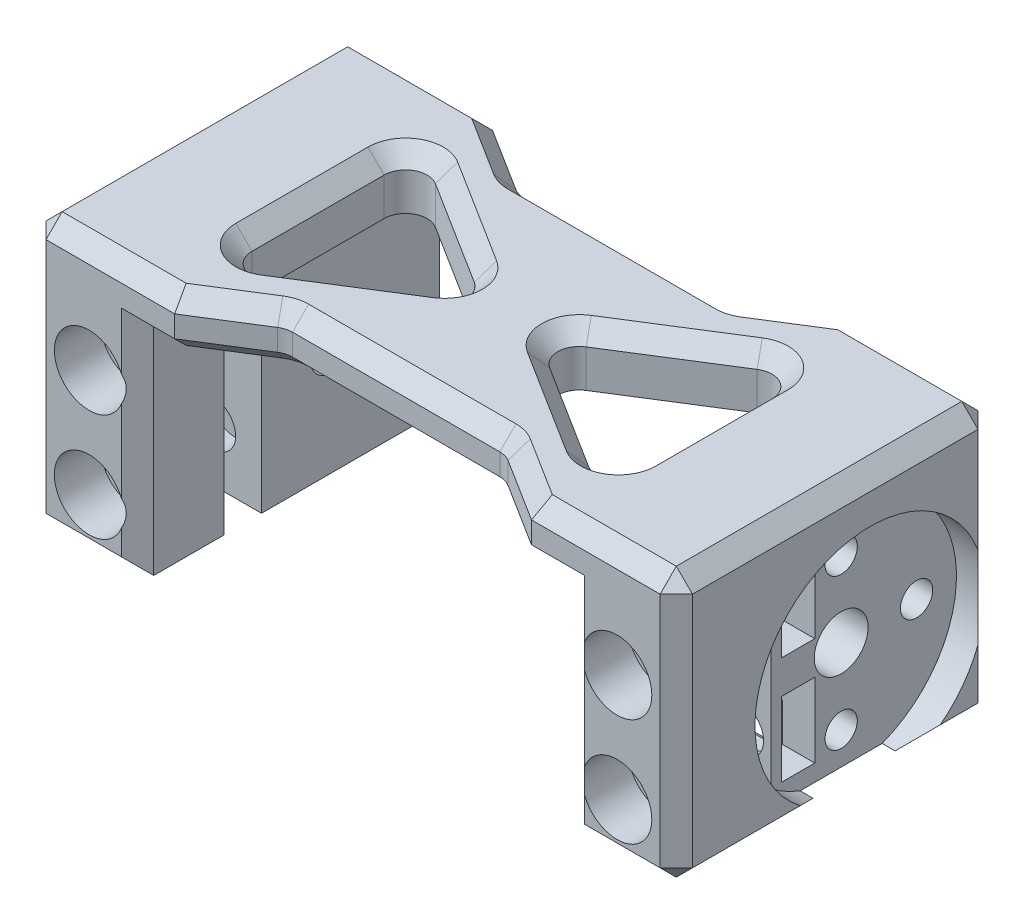
SolidWorks part; units mm, degrees
ref_plane "Ebene vorne" through (0, 0, 0) normal (0, 0, 1) x (1, 0, 0)
ref_plane "Ebene oben" through (0, 0, 0) normal (0, 1, 0) x (1, 0, 0)
ref_plane "Ebene rechts" through (0, 0, 0) normal (1, 0, 0) x (0, 0, -1)
sketch "Sketch1" plane through (0, 0, 0) normal (0, 0, 1) x (1, 0, 0)
  line L0 (-24.5, 10) -> (-24.5, -10) construction
  line L5 (30, -10) -> (20, -10)
  line L6 (30, -10) -> (30, 10)
  line L11 (30, 10) -> (-30, 10)
  line L12 (-30, -10) -> (-30, 10)
  line L21 (30, -10) -> (-30, 10) construction
  line L23 (30, 10) -> (-30, -10) construction
  line L29 (24.5, 10) -> (24.5, -10) construction
  line L30 (-20, -10) -> (-30, -10)
  line L32 (20, -10) -> (20, 10)
  line L33 (20, 10) -> (-20, 10)
  line L35 (-20, -10) -> (-20, 10)
  line L36 (20, -10) -> (-20, 10) construction
  line L37 (20, 10) -> (-20, -10) construction
  line L39 (-30, 10) -> (30, 10)
  line L40 (-30, 10) -> (-30, 15)
  line L41 (-30, 15) -> (30, 15)
  line L42 (30, 10) -> (30, 15)
  circle A4 centre (-24.5, 5) radius 2.1
  circle A5 centre (-24.5, -5) radius 2.1
  circle A6 centre (24.5, 5) radius 2.1
  circle A7 centre (24.5, -5) radius 2.1
  point P0 (0, 0)
  point P10 (-24.5, 0)
  point P12 (0, 0)
  dimension "D7" = 5
  dimension "D11" = 4.2
  dimension "D1" = 60
  dimension "D2" = 20
  dimension "D3" = 24.5
  dimension "D4" = 24.5
  dimension "D5" = 40
  dimension "D6" = 5
  dimension "D8" = 5
  dimension "D9" = 10
  dimension "D10" = 10
extrude "Boss-Extrude1" add sketch "Sketch1" against normal blind 8
sketch "Sketch5" plane through (0, 0, -8) normal (0, 0, -1) x (-1, 0, 0)
  line L0 (30, -10) -> (30, 15) construction
  line L2 (27.75, -10) -> (27.75, 10)
  line L3 (27.75, 10) -> (-27.75, 10)
  line L4 (-27.75, -10) -> (-27.75, 10)
  line L5 (27.75, -10) -> (-27.75, 10) construction
  line L6 (27.75, 10) -> (-27.75, -10) construction
  line L7 (-30, -10) -> (-30, 15) construction
  line L8 (30, 15) -> (-30, 15) construction
  line L9 (30, -10) -> (30, 15)
  line L10 (-30, -10) -> (-30, 15)
  line L11 (30, 15) -> (-30, 15)
  line L12 (-27.75, -10) -> (-30, -10)
  line L13 (27.75, -10) -> (30, -10)
  line L14 (-30, -10) -> (-20, -10) construction
  point P0 (0, 0)
  dimension "D1" = 20
  dimension "D2" = 55.5
extrude "Boss-Extrude2" add sketch "Sketch5" along normal blind 3.5
sketch "Sketch6" plane through (0, 0, -11.5) normal (0, 0, -1) x (-1, 0, 0)
  line L3 (-27.75, -10) -> (-20, -10)
  line L4 (-20, 10) -> (-20, -10)
  line L7 (27.75, -10) -> (20, -10)
  line L8 (-27.75, -10) -> (-27.75, 10)
  line L9 (-27.75, 10) -> (27.75, 10)
  line L10 (27.75, 10) -> (27.75, -10)
  line L11 (27.75, -10) -> (30, -10)
  line L12 (30, -10) -> (30, 15)
  line L13 (30, 15) -> (-30, 15)
  line L14 (-30, 15) -> (-30, -10)
  line L15 (-30, -10) -> (-27.75, -10)
  line L17 (-20, 10) -> (20, 10)
  line L19 (27.75, -10) -> (30, -10)
  line L20 (30, -10) -> (30, 15)
  line L21 (30, 15) -> (-30, 15)
  line L22 (-30, 15) -> (-30, -10)
  line L23 (-30, -10) -> (-27.75, -10)
  line L24 (20, 10) -> (20, -10)
  dimension "D1" = 0
extrude "Boss-Extrude3" add sketch "Sketch6" along normal blind 18
sketch "Sketch7" plane through (30, 0, 0) normal (1, 0, 0) x (0, 0, -1)
  line L0 (0, 0) -> (29.5, 0) construction
  line L1 (29.5, 15) -> (29.5, -10) construction
  circle A0 centre (18, 0) radius 10.1
  circle A1 centre (11, 0) radius 1.5
  circle A2 centre (25, 0) radius 1.5
  circle A3 centre (18, 7) radius 1.5
  circle A4 centre (18, -7) radius 1.5
  circle A5 centre (18, 0) radius 2.5
  dimension "D1" = 20.2
  dimension "D3" = 3
  dimension "D7" = 7
  dimension "D8" = 5
  dimension "D2" = 18
  dimension "D4" = 7
  dimension "D5" = 7
  dimension "D6" = 7
extrude "Cut-Extrude1" cut sketch "Sketch7" against normal blind 10 contours A3 | A2 L0 | L0 A2 | A4 | L0 A5 | A5 L0 | A1
sketch "Sketch8" plane through (30, 0, 0) normal (1, 0, 0) x (0, 0, -1)
  line L0 (14, 15) -> (14, -10) construction
  line L1 (29.5, 15) -> (0, 15) construction
  line L2 (29.5, -10) -> (0, -10) construction
  line L3 (0, -10) -> (0, 15) construction
  line L5 (12.45, 8.45) -> (15.55, 8.45)
  line L6 (12.45, 8.45) -> (12.45, 1.55)
  line L7 (12.45, 1.55) -> (15.55, 1.55)
  line L8 (15.55, 8.45) -> (15.55, 1.55)
  line L9 (12.45, 8.45) -> (15.55, 1.55) construction
  line L10 (12.45, 1.55) -> (15.55, 8.45) construction
  line L11 (15.55, -8.45) -> (12.45, -8.45)
  line L12 (15.55, -8.45) -> (15.55, -1.55)
  line L13 (15.55, -1.55) -> (12.45, -1.55)
  line L14 (12.45, -8.45) -> (12.45, -1.55)
  line L15 (15.55, -8.45) -> (12.45, -1.55) construction
  line L16 (15.55, -1.55) -> (12.45, -8.45) construction
  point P8 (14, 5)
  point P13 (14, -5)
  dimension "D1" = 14
  dimension "D2" = 6.9
  dimension "D3" = 3.1
  dimension "D4" = 10
  dimension "D5" = 5
extrude "Cut-Extrude3" cut sketch "Sketch8" against normal blind 13
sketch "Sketch13" plane through (30, 0, 0) normal (1, 0, 0) x (0, 0, -1)
  circle A0 centre (18, 7) radius 3.225
  circle A1 centre (25, 0) radius 3.225
  circle A2 centre (18, -7) radius 3.225
  dimension "D1" = 6.45
extrude "Cut-Extrude4" cut sketch "Sketch13" along normal blind 4.3 from surface at -10 starting at face at (20, 5, -14)
sketch "Sketch14" plane through (-30, 0, 0) normal (-1, 0, 0) x (0, 0, 1)
  line L0 (0, 0) -> (-29.5, 0) construction
  line L1 (-29.5, -10) -> (-29.5, 15) construction
  circle A0 centre (-18, 0) radius 4
  dimension "D2" = 8
  dimension "D1" = 18
extrude "Boss-Extrude4" add sketch "Sketch14" along normal blind 5
sketch "Sketch15" plane through (-30, 0, 0) normal (-1, 0, 0) x (0, 0, 1)
  circle A1 centre (-18, 0) radius 4 construction
  arc A3 (-19.1646, -3.8267) -> (-19.1646, 3.8267) centre (-18, 0) ccw
  circle A4 centre (-18, 0) radius 6
  circle A5 centre (-18, 0) radius 7.5
  dimension "D2" = 12
  dimension "D1" = 18
extrude "Boss-Extrude5" add sketch "Sketch15" along normal blind 1
sketch "Sketch16" plane through (0, 0, 0) normal (0, 0, 1) x (1, 0, 0)
  circle A0 centre (-24.5, 5) radius 3.225
  circle A1 centre (24.5, 5) radius 3.225
  circle A2 centre (24.5, -5) radius 3.225
  circle A3 centre (-24.5, -5) radius 3.225
  dimension "D1" = 6.45
extrude "Cut-Extrude5" cut sketch "Sketch16" against normal blind 4.3
sketch "Sketch18" plane through (-35, 0, 0) normal (-1, 0, 0) x (0, 0, 1)
  circle A0 centre (-18, 0) radius 1.95
  dimension "D1" = 3.9
extrude "Cut-Extrude7" cut sketch "Sketch18" against normal blind 15
sketch "Sketch19" plane through (0, 0, -11.5) normal (0, 0, 1) x (1, 0, 0)
  circle A0 centre (24.5, 5) radius 2.1
  circle A1 centre (24.5, -5) radius 2.1
  circle A2 centre (-24.5, -5) radius 2.1
  circle A3 centre (-24.5, 5) radius 2.1
extrude "Cut-Extrude8" cut sketch "Sketch19" against normal blind 2
sketch "Sketch20" plane through (30, 0, 0) normal (1, 0, 0) x (0, 0, -1)
  circle A0 centre (18, 0) radius 10.7
  dimension "D1" = 21.4
extrude "Cut-Extrude9" cut sketch "Sketch20" against normal blind 2.7
sketch "Sketch21" plane through (0, 15, 0) normal (0, 1, 0) x (1, 0, 0)
  line L0 (0, 29.5) -> (0, 0) construction
  line L1 (-30, 29.5) -> (30, 29.5) construction
  line L2 (30, 14.75) -> (-30, 14.75) construction
  line L3 (30, 29.5) -> (30, 0) construction
  line L4 (-30, 29.5) -> (-30, 0) construction
  line L5 (9.6225, 25.5) -> (-9.6225, 25.5)
  line L6 (-10.6874, 25.8071) -> (-16.5582, 29.5)
  line L7 (-16.5582, 29.5) -> (16.5582, 29.5)
  line L8 (-5.1913, 16.4429) -> (-14.9351, 22.5721)
  line L9 (-18, 20.8792) -> (-18, 8.6208)
  line L10 (-14.9351, 6.9279) -> (-5.1913, 13.0571)
  line L11 (-30, 0) -> (30, 0) construction
  line L13 (-10.6874, 3.6929) -> (-16.5582, 0)
  line L14 (9.6225, 4) -> (-9.6225, 4)
  line L16 (-16.5582, 0) -> (16.5582, 0)
  line L17 (10.6874, 3.6929) -> (16.5582, 0)
  line L18 (14.9351, 6.9279) -> (5.1913, 13.0571)
  line L19 (18, 20.8792) -> (18, 8.6208)
  line L20 (5.1913, 16.4429) -> (14.9351, 22.5721)
  line L21 (10.6874, 25.8071) -> (16.5582, 29.5)
  arc A0 (10.6874, 3.6929) -> (9.6225, 4) centre (9.6225, 2) ccw
  arc A1 (-10.6874, 3.6929) -> (-9.6225, 4) centre (-9.6225, 2) cw
  arc A2 (-9.6225, 25.5) -> (-10.6874, 25.8071) centre (-9.6225, 27.5) cw
  arc A3 (10.6874, 25.8071) -> (9.6225, 25.5) centre (9.6225, 27.5) cw
  arc A4 (14.9351, 6.9279) -> (18, 8.6208) centre (16, 8.6208) ccw
  arc A5 (18, 20.8792) -> (14.9351, 22.5721) centre (16, 20.8792) ccw
  arc A6 (5.1913, 13.0571) -> (5.1913, 16.4429) centre (6.2562, 14.75) cw
  arc A7 (-5.1913, 16.4429) -> (-5.1913, 13.0571) centre (-6.2562, 14.75) cw
  arc A8 (-18, 8.6208) -> (-14.9351, 6.9279) centre (-16, 8.6208) ccw
  arc A9 (-14.9351, 22.5721) -> (-18, 20.8792) centre (-16, 20.8792) ccw
  point P16 (0, 14.75)
  point P25 (0, 4)
  point P29 (0, 25.5)
  point P32 (10.1992, 4)
  point P35 (-10.1992, 4)
  point P38 (-10.1992, 25.5)
  point P41 (10.1992, 25.5)
  point P44 (18, 5)
  point P47 (18, 24.5)
  point P50 (2.5, 14.75)
  point P53 (-2.5, 14.75)
  point P56 (-18, 5)
  point P59 (-18, 24.5)
  dimension "D7" = 2
  dimension "D1" = 2.5
  dimension "D2" = 5
  dimension "D3" = 5
  dimension "D4" = 12
  dimension "D5" = 5
  dimension "D6" = 4
extrude "Cut-Extrude10" cut sketch "Sketch21" against normal through all
chamfer "Chamfer1" distance 1.5 angle 45 57 edges at (18.2791, 10, 0) (-20, 0, 0) (-25, -10, 0) (-30, 2.5, 0) (-23.2791, 15, 0) (30, 2.5, 0) (25, -10, 0) (20, 0, 0) (-30, -10, -14.75) (-30, 15, -14.75) (30, 15, -14.75) (30, -10, -25.6533) (30, -10, -7.0967) (-18.2791, 10, -29.5) (23.2791, 15, -29.5) (23.2791, 15, 0) (-18.2791, 10, 0) (10.1766, 10, -25.5783) (0, 10, -25.5) (-10.1766, 10, -25.5783) (13.6228, 10, -27.6535) (-13.6228, 10, -27.6535) (13.6228, 15, -27.6535) (-13.6228, 15, -27.6535) (-10.1766, 15, -25.5783) (0, 15, -25.5) (10.1766, 15, -25.5783) (-4.2562, 15, -14.75) (-10.0632, 15, -19.5075) (-16.967, 15, -22.6298) (-18, 15, -14.75) (-16.967, 15, -6.8702) (-10.0632, 15, -9.9925) (16.967, 15, -6.8702) (18, 15, -14.75) (16.967, 15, -22.6298) (10.0632, 15, -19.5075) (4.2562, 15, -14.75) (10.0632, 15, -9.9925) (-10.1766, 10, -3.9217) (0, 10, -4) (10.1766, 10, -3.9217) (-13.6228, 10, -1.8465) (13.6228, 10, -1.8465) (13.6228, 15, -1.8465) (10.1766, 15, -3.9217) (0, 15, -4) (-10.1766, 15, -3.9217) (-13.6228, 15, -1.8465) (25, -10, -29.5) (20, 0, -29.5) (18.2791, 10, -29.5) (-20, 0, -29.5) (-25, -10, -29.5) (-30, 2.5, -29.5) (-23.2791, 15, -29.5) (30, 2.5, -29.5)
